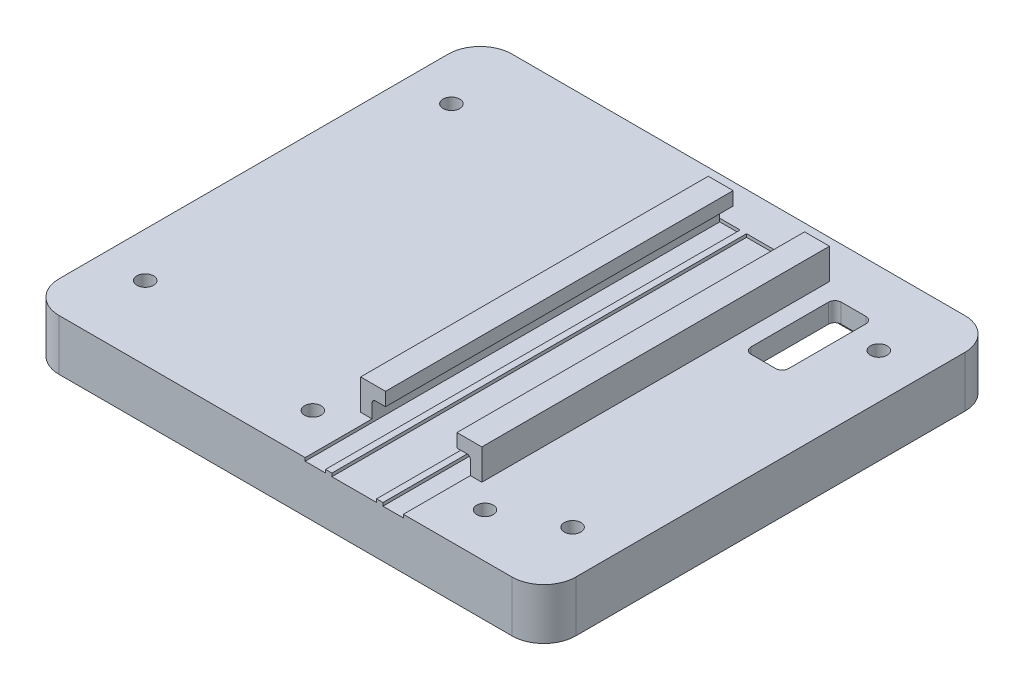
SolidWorks part; units mm, degrees
ref_plane "Alzado" through (0, 0, 0) normal (0, 0, 1) x (1, 0, 0)
ref_plane "Planta" through (0, 0, 0) normal (0, 1, 0) x (1, 0, 0)
ref_plane "Vista lateral" through (0, 0, 0) normal (1, 0, 0) x (0, 0, -1)
sketch "Croquis9" plane through (0, 0, 0) normal (0, 0, 1) x (1, 0, 0)
  line L0 (0, 17.7123) -> (0, -23.4478) construction
  line L1 (0, 10.708) -> (-22, 10.708)
  line L2 (-22, 10.708) -> (-22, 7.708)
  line L3 (-22, 7.708) -> (-19, 7.708)
  line L4 (-19, 7.708) -> (-4.5, 6.708)
  line L5 (-4.5, 6.708) -> (-4.5, -8.292)
  line L6 (-4.5, -8.292) -> (0, -8.292)
  line L7 (0, 10.708) -> (0, -8.292)
  dimension "D1" = 22
  dimension "D2" = 4.5
  dimension "D3" = 3
  dimension "D4" = 1
  dimension "D5" = 15
  dimension "D6" = 3
  dimension "D7" = 19
revolve "Revolución3" add sketch "Croquis9" angle 360 about L0
sketch "Croquis17" plane through (0, 0, 0) normal (1, 0, 0) x (0, 0, -1)
  line L0 (-4.5, -8.292) -> (4.5, -8.292) construction
  circle A0 centre (0, -2.292) radius 1.5
  dimension "D1" = 3
  dimension "D2" = 6
extrude "Cortar-Extruir7" cut sketch "Croquis17" along normal up to next
sketch "Croquis18" plane through (0, 10.708, 0) normal (0, 1, 0) x (1, 0, 0)
  line L1 (2.1, 2.2804) -> (2.1, -2.2804)
  arc A1 (2.1, 2.2804) -> (2.1, -2.2804) centre (0, 0) ccw
  dimension "D1" = 6.2
  dimension "D2" = 1
extrude "Cortar-Extruir10" cut sketch "Croquis18" against normal blind 5 from offset 3 offset against normal yes
sketch "Croquis21" plane through (0, 0, 0) normal (0, 0, 1) x (1, 0, 0)
  line L0 (0, 3.5811) -> (0, -1.3759) construction
  line L1 (0, 1.8085) -> (-3.1, 1.8085)
  line L2 (-3.1, 1.8085) -> (-3.1, -1.6716)
  line L3 (-3.1, -1.6716) -> (0, -1.6716)
  line L4 (0, 1.8085) -> (0, -1.6716)
  dimension "D1" = 3.1
revolve "Cortar-Revolución1" cut sketch "Croquis21" angle 360 about L0
chamfer "Chaflán1" [suppressed] distance 0.5 angle 45
sketch "Croquis22" plane through (0, 10.708, 0) normal (0, 1, 0) x (1, 0, 0)
  line L1 (-37.5, -32.5) -> (37.5, -32.5)
  line L2 (-37.5, -32.5) -> (-37.5, 32.5)
  line L3 (-37.5, 32.5) -> (37.5, 32.5)
  line L4 (37.5, -32.5) -> (37.5, 32.5)
  line L5 (-37.5, -32.5) -> (37.5, 32.5) construction
  line L6 (-37.5, 32.5) -> (37.5, -32.5) construction
  point P0 (0, 0)
  dimension "D1" = 65
  dimension "D2" = 75
extrude "Saliente-Extruir1" add sketch "Croquis22" against normal up to surface (3 mm away) up to face at (0, 7.708, 19)
fillet "Redondeo1" radius 2 4 edges at (-37.5, 9.208, -32.5) (37.5, 9.208, -32.5) (37.5, 9.208, 32.5) (-37.5, 9.208, 32.5)
sketch "Croquis23" plane through (0, 10.708, 0) normal (0, 1, 0) x (1, 0, 0)
  circle A0 centre (-33.5, 24) radius 1.3
  circle A1 centre (-33.5, -24) radius 1.3
  circle A2 centre (33.5, -24) radius 1.3
  circle A3 centre (33.5, 24) radius 1.3
  dimension "D1" = 2.6
  dimension "D4" = 48
  dimension "D3" = 33.5
  dimension "D2" = 67
  dimension "D5" = 24
extrude "Cortar-Extruir11" cut sketch "Croquis23" against normal blind 2
sketch "Croquis24" plane through (0, 10.708, 0) normal (0, 1, 0) x (1, 0, 0)
  line L0 (6.27, -32.5) -> (6.27, -36.5)
  line L1 (3.27, 29.5) -> (18.27, 29.5)
  line L2 (3.27, 29.5) -> (3.27, -32.5)
  line L3 (3.27, -32.5) -> (18.27, -32.5)
  line L4 (18.27, 29.5) -> (18.27, -32.5)
  line L5 (6.27, 29.5) -> (7.27, 29.5)
  line L6 (6.27, 29.5) -> (6.27, -32.5)
  line L7 (6.27, -32.5) -> (7.27, -32.5)
  line L8 (7.27, 29.5) -> (7.27, -32.5)
  line L9 (14.27, 29.5) -> (15.27, 29.5)
  line L10 (14.27, 29.5) -> (14.27, -32.5)
  line L11 (14.27, -32.5) -> (15.27, -32.5)
  line L12 (15.27, 29.5) -> (15.27, -32.5)
  line L13 (35.5, 32.5) -> (-35.5, 32.5) construction
  line L14 (-35.5, -32.5) -> (35.5, -32.5) construction
  line L15 (3.27, -32.5) -> (18.27, -32.5)
  line L16 (3.27, -32.5) -> (3.27, -36.5)
  line L17 (3.27, -36.5) -> (18.27, -36.5)
  line L18 (18.27, -32.5) -> (18.27, -36.5)
  line L19 (6.27, -36.5) -> (7.27, -36.5)
  line L20 (7.27, -36.5) -> (7.27, -32.5)
  line L21 (14.27, -32.5) -> (14.27, -36.5)
  line L22 (15.27, -32.5) -> (15.27, -36.5)
  dimension "D1" = 3
  dimension "D2" = 15
  dimension "D3" = 1
  dimension "D4" = 1
  dimension "D5" = 3.27
  dimension "D6" = 3
  dimension "D7" = 3
  dimension "D8" = 4
extrude "Cortar-Extruir12" cut sketch "Croquis24" against normal blind 0.5 contours L6 L1 L2 L3 | L10 L1 L8 L3 | L1 L12 L3 L4 region at (4.77, 10.708, 1.5) region at (10.77, 10.708, 1.5) region at (16.77, 10.708, 1.5)
sketch "Croquis25" plane through (0, 10.708, 0) normal (0, 1, 0) x (1, 0, 0)
  line L0 (3.27, 29.5) -> (3.27, -32.5) construction
  line L1 (18.27, 29.5) -> (18.27, -32.5) construction
  line L3 (-35.5, -32.5) -> (3.27, -32.5) construction
  circle A0 centre (-2.73, -28.5) radius 1.3
  circle A1 centre (24.27, -28.5) radius 1.3
  circle A2 centre (33.5, -24) radius 1.3 construction
  circle A3 centre (33.5, -24) radius 1.3 construction
  dimension "D2" = 6
  dimension "D1" = 6
  dimension "D4" = 4
extrude "Cortar-Extruir13" cut sketch "Croquis25" against normal blind 2
sketch "Croquis26" plane through (0, 10.708, 0) normal (0, 1, 0) x (1, 0, 0)
  line L1 (22.988, 27.6308) -> (28.8765, 27.6308)
  line L2 (22.988, 27.6308) -> (22.988, 13.4757)
  line L3 (22.988, 13.4757) -> (28.8765, 13.4757)
  line L4 (28.8765, 27.6308) -> (28.8765, 13.4757)
extrude "Cortar-Extruir14" cut sketch "Croquis26" against normal blind 10
sketch "Croquis30" plane through (0, 0, 32.5) normal (0, 0, 1) x (1, 0, 0)
  line L0 (3.27, 10.708) -> (1.27, 10.708)
  line L1 (1.27, 10.708) -> (1.27, 15.508)
  line L2 (1.27, 15.508) -> (5.17, 15.508)
  line L3 (5.17, 15.508) -> (5.17, 13.408)
  line L4 (5.17, 13.408) -> (3.27, 13.408)
  line L5 (3.27, 13.408) -> (3.27, 10.708)
  line L6 (18.27, 10.708) -> (20.27, 10.708)
  line L7 (18.27, 10.708) -> (35.5, 10.708) construction
  line L8 (20.27, 10.708) -> (20.27, 15.508)
  line L9 (20.27, 15.508) -> (16.37, 15.508)
  line L10 (16.37, 15.508) -> (16.37, 13.408)
  line L11 (16.37, 13.408) -> (18.27, 13.408)
  line L12 (18.27, 13.408) -> (18.27, 10.708)
  dimension "D1" = 1.9
  dimension "D2" = 4.8
  dimension "D3" = 2
  dimension "D4" = 2.7
extrude "Saliente-Extruir2" add sketch "Croquis30" against normal up to surface (62 mm away) from offset 7.5 up to face at (4.77, 10.458, -29.5) offset against normal yes
sketch "Croquis31" plane through (0, 0, 32.5) normal (0, 0, 1) x (1, 0, 0)
  line L0 (3.27, 13.408) -> (5.17, 13.408) construction
  line L1 (3.27, 10.208) -> (3.07, 10.208)
  line L2 (3.27, 10.208) -> (3.27, 13.408)
  line L3 (3.27, 13.408) -> (3.07, 13.408)
  line L4 (3.07, 10.208) -> (3.07, 13.408)
  line L5 (18.27, 10.208) -> (18.47, 10.208)
  line L6 (18.27, 10.208) -> (18.27, 13.408)
  line L7 (18.27, 13.408) -> (18.47, 13.408)
  line L8 (18.47, 10.208) -> (18.47, 13.408)
  line L9 (16.37, 13.408) -> (18.27, 13.408) construction
  dimension "D1" = 0.2
  dimension "D2" = 0.2
extrude "Cortar-Extruir17" cut sketch "Croquis31" against normal up to surface (62 mm away) and the other way blind 10 up to face at (4.77, 10.458, -29.5)
fillet "Redondeo2" radius 0.5 2 edges at (18.47, 13.408, -2.25) (3.07, 13.408, -2.25)
fillet "Redondeo3" radius 1 4 edges at (28.8765, 9.208, -13.4757) (22.988, 9.208, -13.4757) (22.988, 9.208, -27.6308) (28.8765, 9.208, -27.6308)
sketch "Croquis33" plane through (0, 10.708, 0) normal (0, 1, 0) x (1, 0, 0)
  circle A1 centre (-33.5, -24) radius 2.6
  circle A2 centre (-33.5, 24) radius 2.6
  circle A3 centre (-2.73, -28.5) radius 2.6
  circle A4 centre (24.27, -28.5) radius 2.6
  circle A5 centre (33.5, -24) radius 2.6
  circle A6 centre (33.5, 24) radius 2.6
  dimension "D1" = 5.2
extrude "Saliente-Extruir3" add sketch "Croquis33" against normal blind 5 from surface starting at face at (25.9322, 7.708, -20.5533)
sketch "Croquis34" plane through (0, 10.708, 0) normal (0, 1, 0) x (1, 0, 0)
  circle A0 centre (-33.5, -24) radius 1.3 construction
  circle A1 centre (-2.73, -28.5) radius 1.3 construction
  circle A2 centre (24.27, -28.5) radius 1.3 construction
  circle A3 centre (33.5, -24) radius 1.3 construction
  circle A4 centre (33.5, 24) radius 1.3 construction
  circle A5 centre (-33.5, 24) radius 1.3 construction
  circle A6 centre (-33.5, -24) radius 1.3
  circle A7 centre (-2.73, -28.5) radius 1.3
  circle A8 centre (24.27, -28.5) radius 1.3
  circle A9 centre (33.5, -24) radius 1.3
  circle A10 centre (33.5, 24) radius 1.3
  circle A11 centre (-33.5, 24) radius 1.3
extrude "Cortar-Extruir18" cut sketch "Croquis34" against normal through all
ref_axis "Eje1" through (33.5, 2.708, -24) along (0, 1, 0)
ref_plane "Plano1" through (0, 0, -24) normal (0, 0, -1) x (-1, 0, 0)
sketch "Croquis37" plane through (0, 0, -24) normal (0, 0, -1) x (-1, 0, 0)
  line L0 (-30.9, 5.208) -> (-29.9, 7.708)
  line L1 (-30.9, 2.708) -> (-30.9, 7.708) construction
  line L2 (-35.5, 7.708) -> (35.5, 7.708) construction
  dimension "D1" = 1
  dimension "D2" = 2.5
rib "Nervio3" sketch "Croquis37" sketch "Croquis37" thickness 1.8 extrusion direction parallel to sketch draft on no parameters "D1"=1.8
pattern_circular "MatrizC3" count 4 every 90 about axis through (33.5, 2.708, -24) along (0, 1, 0) of "Nervio3"
pattern_linear "MatrizL3" count 2 spacing 67.1 along (-1, 0, 0) count 2 spacing 48 along (0, 0, 1) of "MatrizC3"
sketch "Croquis38" plane through (0, 7.708, 0) normal (0, -1, 0) x (1, 0, 0)
  line L24 (37.5, 30.5) -> (37.5, -30.5) construction
  line L25 (35.5, -32.5) -> (-35.5, -32.5) construction
  line L26 (-35.5, 32.5) -> (35.5, 32.5) construction
  line L27 (-37.5, -30.5) -> (-37.5, 30.5) construction
  line L28 (-40.5, 30.5) -> (-40.5, -30.5)
  line L29 (-35.5, -35.5) -> (35.5, -35.5)
  line L30 (40.5, -30.5) -> (40.5, 30.5)
  line L31 (35.5, 35.5) -> (-35.5, 35.5)
  line L32 (-40.5, 30.5) -> (-40.5, -30.5)
  line L33 (-35.5, -35.5) -> (35.5, -35.5)
  line L34 (40.5, -30.5) -> (40.5, 30.5)
  line L35 (35.5, 35.5) -> (-35.5, 35.5)
  line L36 (37.5, 30.5) -> (37.5, -30.5)
  line L37 (35.5, -32.5) -> (-35.5, -32.5)
  line L38 (-35.5, 32.5) -> (35.5, 32.5)
  line L39 (-37.5, -30.5) -> (-37.5, 30.5)
  arc A18 (37.5, 30.5) -> (35.5, 32.5) centre (35.5, 30.5) ccw construction
  arc A19 (35.5, -32.5) -> (37.5, -30.5) centre (35.5, -30.5) ccw construction
  arc A20 (-37.5, -30.5) -> (-35.5, -32.5) centre (-35.5, -30.5) ccw construction
  arc A21 (-35.5, 32.5) -> (-37.5, 30.5) centre (-35.5, 30.5) ccw construction
  arc A22 (-35.5, 35.5) -> (-40.5, 30.5) centre (-35.5, 30.5) ccw
  arc A23 (-40.5, -30.5) -> (-35.5, -35.5) centre (-35.5, -30.5) ccw
  arc A24 (35.5, -35.5) -> (40.5, -30.5) centre (35.5, -30.5) ccw
  arc A25 (40.5, 30.5) -> (35.5, 35.5) centre (35.5, 30.5) ccw
  arc A26 (-35.5, 35.5) -> (-40.5, 30.5) centre (-35.5, 30.5) ccw
  arc A27 (-40.5, -30.5) -> (-35.5, -35.5) centre (-35.5, -30.5) ccw
  arc A28 (35.5, -35.5) -> (40.5, -30.5) centre (35.5, -30.5) ccw
  arc A29 (40.5, 30.5) -> (35.5, 35.5) centre (35.5, 30.5) ccw
  arc A30 (37.5, 30.5) -> (35.5, 32.5) centre (35.5, 30.5) ccw
  arc A31 (35.5, -32.5) -> (37.5, -30.5) centre (35.5, -30.5) ccw
  arc A32 (-37.5, -30.5) -> (-35.5, -32.5) centre (-35.5, -30.5) ccw
  arc A33 (-35.5, 32.5) -> (-37.5, 30.5) centre (-35.5, 30.5) ccw
  dimension "D1" = 3
extrude "Saliente-Extruir4" add sketch "Croquis38" along normal blind 5 and the other way up to surface (3 mm away) other way up to face at (-33.5, 10.708, 25.3)
sketch "Croquis39" plane through (0, -8.292, 0) normal (0, -1, 0) x (1, 0, 0)
  circle A0 centre (0, 0) radius 3.1
  dimension "D1" = 6.2
extrude "Cortar-Extruir19" cut sketch "Croquis39" against normal blind 11
sketch "Croquis41" plane through (0, 10.708, 0) normal (0, 1, 0) x (1, 0, 0)
  line L0 (35.5, -35.5) -> (-35.5, -35.5) construction
  line L1 (3.07, -32.5) -> (6.27, -32.5)
  line L2 (3.07, -32.5) -> (3.07, -35.5)
  line L3 (3.07, -35.5) -> (6.27, -35.5)
  line L4 (6.27, -32.5) -> (6.27, -35.5)
  line L5 (18.47, -32.5) -> (15.27, -32.5) construction
  line L6 (7.27, -32.5) -> (14.27, -32.5)
  line L7 (7.27, -32.5) -> (7.27, -35.5)
  line L8 (7.27, -35.5) -> (14.27, -35.5)
  line L9 (14.27, -32.5) -> (14.27, -35.5)
  line L10 (15.27, -32.5) -> (18.47, -32.5)
  line L11 (15.27, -32.5) -> (15.27, -35.5)
  line L12 (15.27, -35.5) -> (18.47, -35.5)
  line L13 (18.47, -32.5) -> (18.47, -35.5)
extrude "Cortar-Extruir20" cut sketch "Croquis41" against normal up to surface (0.5 mm away) up to face at (10.77, 10.208, 1.5)
